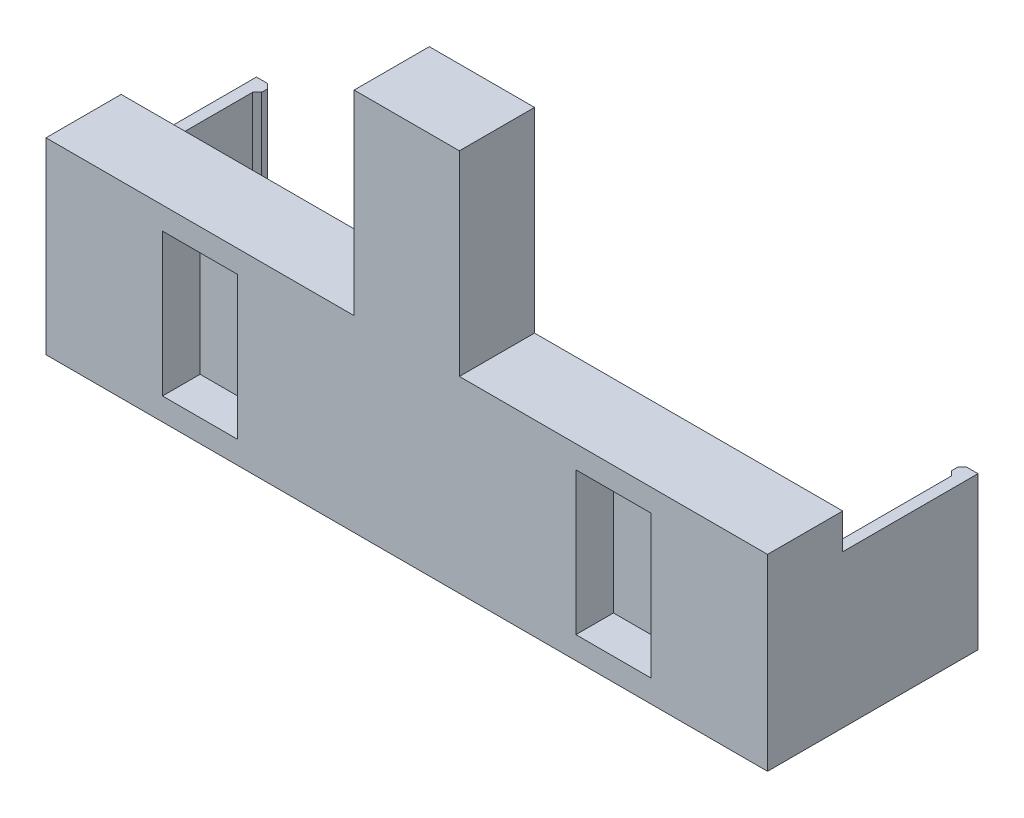
SolidWorks part; units mm, degrees
ref_plane "Front Plane" through (0, 0, 0) normal (0, 0, 1) x (1, 0, 0)
ref_plane "Top Plane" through (0, 0, 0) normal (0, 1, 0) x (1, 0, 0)
ref_plane "Right Plane" through (0, 0, 0) normal (1, 0, 0) x (0, 0, -1)
sketch "Display Rough Dim" plane through (0, 0, 0) normal (0, 0, 1) x (1, 0, 0)
  line L1 (-46.5, 48.5) -> (46.5, 48.5)
  line L2 (-46.5, 48.5) -> (-46.5, -48.5)
  line L3 (-46.5, -48.5) -> (46.5, -48.5)
  line L4 (46.5, 48.5) -> (46.5, -48.5)
  line L5 (-46.5, 48.5) -> (46.5, -48.5) construction
  line L6 (-46.5, -48.5) -> (46.5, 48.5) construction
  point P0 (0, 0)
  dimension "D1" = 93
  dimension "D2" = 97
sketch "Sketch1" plane through (0, 0, 0) normal (0, 0, 1) x (1, 0, 0)
  line L0 (-46.5, 48.5) -> (46.5, 48.5) construction
  line L1 (-48, 12.5) -> (48, 12.5)
  line L2 (-48, 12.5) -> (-48, -12.5)
  line L3 (-48, -12.5) -> (48, -12.5)
  line L4 (48, 12.5) -> (48, -12.5)
  line L5 (-48, 12.5) -> (48, -12.5) construction
  line L6 (-48, -12.5) -> (48, 12.5) construction
  line L7 (-7, 12.5) -> (-7, 38.5)
  line L8 (-7, 38.5) -> (7, 38.5)
  line L9 (7, 38.5) -> (7, 12.5)
  line L10 (46.5, 12.5) -> (46.5, -12.5)
  line L11 (46.5, 48.5) -> (46.5, -48.5) construction
  line L12 (-46.5, 12.5) -> (-46.5, -12.5)
  line L13 (-46.5, 48.5) -> (-46.5, -48.5) construction
  circle A0 centre (0, 31.5) radius 2
  point P0 (0, 0)
  point P14 (0, 38.5)
  dimension "D3" = 17
  dimension "D4" = 4
  dimension "D6" = 7
  dimension "D1" = 96
  dimension "D2" = 25
  dimension "D5" = 7
extrude "Boss-Extrude1" add sketch "Sketch1" along normal blind 10 contours L1 L12 L3 L10 | L12 L1 L2 L3 | L1 L10 L3 L4 | L9 L8 L7 L1 A0 | A0 region at (-47.25, 0, 0) region at (0, 0, 0) region at (0, 25.2855, 0) region at (47.25, 0, 0) region at (0, 31.5, 0)
extrude "Boss-Extrude2" add sketch "Sketch1<3>" against normal blind 18 contours L1 L10 L3 L4 | L12 L1 L2 L3 region at (-47.25, 0, 0) region at (47.25, 0, 0)
sketch "Sketch1<3>" plane through (0, 0, 0) normal (0, 0, 1) x (1, 0, 0) same geometry as "Sketch1"
extrude "Boss-Extrude3" add sketch "Sketch1<4>" against normal blind 5 contours A0
sketch "Sketch1<4>" plane through (0, 0, 0) normal (0, 0, 1) x (1, 0, 0) same geometry as "Sketch1"
sketch "Sketch5" plane through (0, 12.5, 0) normal (0, 1, 0) x (1, 0, 0)
  line L0 (-46.5, 18) -> (-45.5, 17)
  line L1 (-45.5, 17) -> (-46.5, 16)
  line L2 (-46.5, 18) -> (-46.5, 0) construction
  line L3 (-46.5, 16) -> (-43, 16) construction
  line L4 (-43, 16) -> (-43, 18) construction
  line L5 (-43, 18) -> (-46.5, 16) construction
  line L6 (-45.9, 17.4) -> (-45.9, 16.6)
  line L7 (0, 0) -> (0, 13.3207) construction
  line L8 (-48, 0) -> (48, 0) construction
  line L9 (45.5, 17) -> (46.5, 16)
  line L10 (46.5, 18) -> (45.5, 17)
  line L11 (45.9, 17.4) -> (45.9, 16.6)
  line L12 (46.5, 16) -> (46.5, 18)
  line M7 (-46.5, 0) -> (-46.5, 18)
  dimension "D1" = 3.5
  dimension "D2" = 2
  dimension "D3" = 135
  dimension "D4" = 0.6
extrude "Boss-Extrude4" add sketch "Sketch5" along direction (0, -1, 0) on the side against the normal up to surface (25 mm away) contours L9 L12 L10 L11 | L6 L0 L1 M7 region at (-46.2429, 12.5, -17) region at (46.2429, 12.5, -17) up to face at (0, -12.5, -6.5)
sketch "Sketch7" plane through (0, 12.5, 0) normal (0, 1, 0) x (1, 0, 0)
  line L0 (46.5, 0) -> (48, 0)
  line L1 (-48, 0) -> (48, 0) construction
  line L3 (-46.5, 0) -> (-48, 0)
  line L4 (-48, 0) -> (48, 0) construction
  line L12 (46.5, 0) -> (7, 0)
  line L13 (7, 0) -> (7, -10)
  line L14 (7, -10) -> (48, -10)
  line L15 (48, -10) -> (48, 18)
  line L16 (48, 18) -> (46.5, 18)
  line L17 (46.5, 18) -> (45.9, 17.4)
  line L18 (45.9, 17.4) -> (45.9, 16.6)
  line L19 (45.9, 16.6) -> (46.5, 16)
  line L20 (46.5, 16) -> (46.5, 0)
  line L21 (46.5, 0) -> (7, 0)
  line L22 (7, 0) -> (7, -10)
  line L23 (7, -10) -> (48, -10)
  line L24 (48, -10) -> (48, 18)
  line L25 (48, 18) -> (46.5, 18)
  line L26 (46.5, 18) -> (45.9, 17.4)
  line L27 (45.9, 17.4) -> (45.9, 16.6)
  line L28 (45.9, 16.6) -> (46.5, 16)
  line L29 (46.5, 16) -> (46.5, 0)
  line L30 (-7, 0) -> (-46.5, 0)
  line L31 (-46.5, 0) -> (-46.5, 16)
  line L32 (-46.5, 16) -> (-45.9, 16.6)
  line L33 (-45.9, 16.6) -> (-45.9, 17.4)
  line L34 (-45.9, 17.4) -> (-46.5, 18)
  line L35 (-46.5, 18) -> (-48, 18)
  line L36 (-48, 18) -> (-48, -10)
  line L37 (-48, -10) -> (-7, -10)
  line L38 (-7, -10) -> (-7, 0)
  line L39 (-7, 0) -> (-46.5, 0)
  line L40 (-46.5, 0) -> (-46.5, 16)
  line L41 (-46.5, 16) -> (-45.9, 16.6)
  line L42 (-45.9, 16.6) -> (-45.9, 17.4)
  line L43 (-45.9, 17.4) -> (-46.5, 18)
  line L44 (-46.5, 18) -> (-48, 18)
  line L45 (-48, 18) -> (-48, -10)
  line L46 (-48, -10) -> (-7, -10)
  line L47 (-7, -10) -> (-7, 0)
  line M22 (48, -10) -> (48, 18)
  line M23 (48, 18) -> (46.5, 18)
  line M24 (46.5, 18) -> (45.9, 17.4)
  line M25 (45.9, 17.4) -> (45.9, 16.6)
  line M26 (45.9, 16.6) -> (46.5, 16)
  line M27 (46.5, 16) -> (46.5, 0)
  dimension "D1" = 0
  dimension "D2" = 0
extrude "Cut-Extrude1" cut sketch "Sketch7" against normal blind 4.7 contours L0 M27 M22 M23 M24 M25 M26 region at (47.2196, 12.5, -9.2414)
extrude "Cut-Extrude2" cut sketch "Sketch7<4>" against normal blind 7 contours L44 L45 L3 L40 L41 L42 L43 region at (-47.2196, 12.5, -9.2414)
sketch "Sketch7<4>" plane through (0, 12.5, 0) normal (0, 1, 0) x (1, 0, 0) same geometry as "Sketch7"
sketch "Sketch8" plane through (0, 0, 10) normal (0, 0, 1) x (1, 0, 0)
  line L0 (-27.5, 12.5) -> (-27.5, 0) construction
  line L1 (-32.5, 9.5) -> (-22.5, 9.5)
  line L2 (-32.5, 9.5) -> (-32.5, -9.5)
  line L3 (-32.5, -9.5) -> (-22.5, -9.5)
  line L4 (-22.5, 9.5) -> (-22.5, -9.5)
  line L5 (-32.5, 9.5) -> (-22.5, -9.5) construction
  line L6 (-32.5, -9.5) -> (-22.5, 9.5) construction
  line L7 (-48, 12.5) -> (-7, 12.5) construction
  line L8 (27.5, 12.5) -> (27.5, 0) construction
  line L9 (7, 12.5) -> (48, 12.5) construction
  line L11 (22.5, 9.5) -> (32.5, 9.5)
  line L12 (22.5, 9.5) -> (22.5, -9.5)
  line L13 (22.5, -9.5) -> (32.5, -9.5)
  line L14 (32.5, 9.5) -> (32.5, -9.5)
  line L15 (22.5, 9.5) -> (32.5, -9.5) construction
  line L16 (22.5, -9.5) -> (32.5, 9.5) construction
  point P0 (-27.5, 0)
  point P18 (0, 0)
  point P19 (0, 0)
  dimension "D1" = 10
  dimension "D2" = 19
extrude "Cut-Extrude3" cut sketch "Sketch8" against normal blind 5
equation "\"DisplayHeight\"= 18mm"
equation "\"DisplayWidth\"= 93mm"
equation "\"DisplayTall\"= 97mm"
